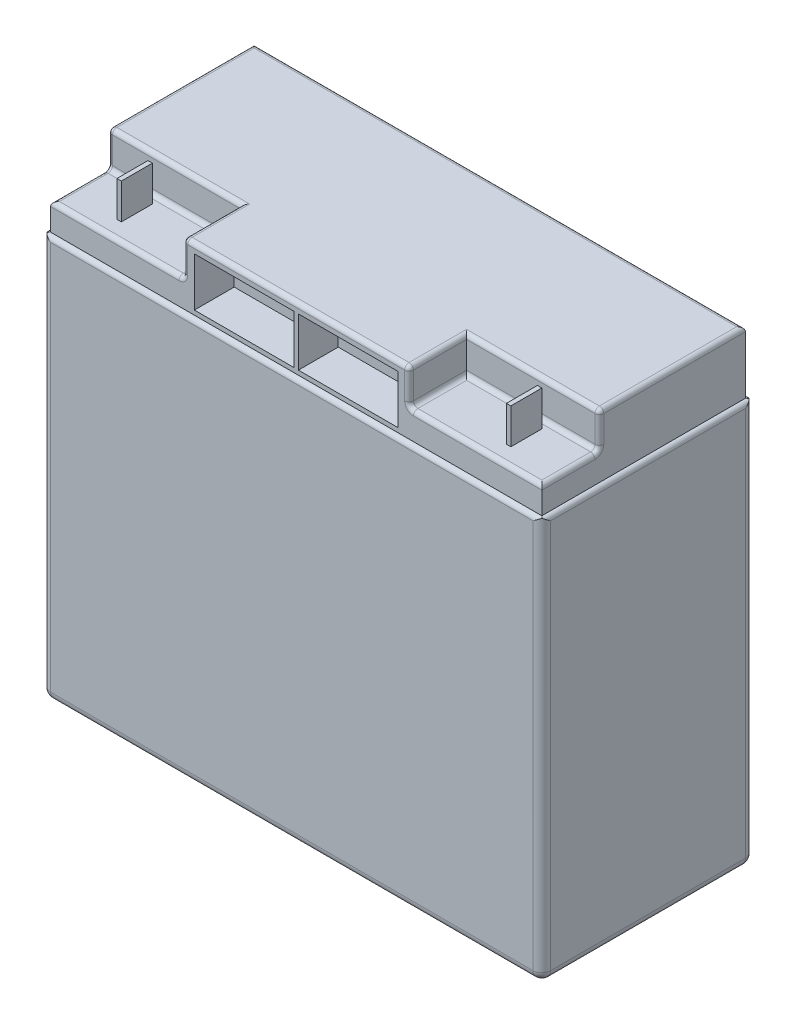
SolidWorks part; units mm, degrees
material "PE Low/Medium Density"
ref_plane "Front Plane" through (0, 0, 0) normal (0, 0, 1) x (1, 0, 0)
ref_plane "Top Plane" through (0, 0, 0) normal (0, 1, 0) x (1, 0, 0)
ref_plane "Right Plane" through (0, 0, 0) normal (1, 0, 0) x (0, 0, -1)
sketch "Sketch1" plane through (0, 0, 0) normal (0, 0, 1) x (1, 0, 0)
  line L0 (-89.6937, -83.3438) -> (89.6938, 83.3437) construction
  line L1 (-89.6938, 83.3437) -> (89.6938, 83.3437)
  line L2 (-89.6938, 83.3437) -> (-89.6937, -83.3438)
  line L3 (-89.6937, -83.3438) -> (89.6938, -83.3438)
  line L4 (89.6938, 83.3437) -> (89.6938, -83.3438)
  dimension "D1" = 166.6875
  dimension "D2" = 179.3875
extrude "Extrude1" add sketch "Sketch1" along normal mid plane 76.2
sketch "Sketch2" plane through (0, 83.3437, 0) normal (0, 1, 0) x (-1, 0, 0)
  line L10 (-89.6938, 38.1) -> (-89.6938, -38.1) construction
  line L11 (-89.6938, 38.1) -> (89.6938, 38.1) construction
  line L12 (-89.6938, -38.1) -> (89.6938, -38.1) construction
  line L13 (89.6938, 38.1) -> (89.6938, -38.1) construction
  line L14 (88.1063, -36.5125) -> (88.1063, 36.5125)
  line L15 (-88.1063, -36.5125) -> (88.1063, -36.5125)
  line L16 (-88.1063, 36.5125) -> (-88.1063, -36.5125)
  line L17 (88.1063, 36.5125) -> (-88.1063, 36.5125)
  line L18 (88.1063, -36.5125) -> (88.1063, 36.5125)
  line L19 (-88.1063, -36.5125) -> (88.1063, -36.5125)
  line L20 (-88.1063, 36.5125) -> (-88.1063, -36.5125)
  line L21 (88.1063, 36.5125) -> (-88.1063, 36.5125)
  line L22 (89.6938, 38.1) -> (89.6938, -38.1)
  line L23 (-89.6938, -38.1) -> (89.6938, -38.1)
  line L24 (-89.6938, 38.1) -> (89.6938, 38.1)
  line L25 (-89.6938, 38.1) -> (-89.6938, -38.1)
  dimension "D1" = 1.5875
extrude "Cut-Extrude1" cut sketch "Sketch2" against normal blind 22.225
sketch "Sketch3" plane through (0, 83.3437, 0) normal (0, 1, 0) x (-1, 0, 0)
  line L1 (-88.1063, 15.875) -> (-40.4812, 15.875)
  line L2 (-88.1063, 15.875) -> (-88.1063, 36.5125)
  line L3 (-88.1063, 36.5125) -> (-40.4812, 36.5125)
  line L4 (-40.4812, 15.875) -> (-40.4812, 36.5125)
  line L5 (88.1063, 15.875) -> (40.4812, 15.875)
  line L6 (88.1063, 15.875) -> (88.1063, 36.5125)
  line L7 (88.1063, 36.5125) -> (40.4812, 36.5125)
  line L8 (40.4812, 15.875) -> (40.4812, 36.5125)
  dimension "D1" = 20.6375
  dimension "D2" = 47.625
extrude "Cut-Extrude2" cut sketch "Sketch3" against normal blind 12.7
sketch "Sketch4" plane through (0, 0, 36.5125) normal (0, 0, 1) x (1, 0, 0)
  line L0 (-40.4813, 83.3437) -> (40.4812, 83.3437) construction
  line L1 (-36.5125, 80.1687) -> (-0.7938, 80.1687)
  line L2 (-36.5125, 80.1687) -> (-36.5125, 62.7062)
  line L3 (-36.5125, 62.7062) -> (-0.7938, 62.7062)
  line L4 (-0.7938, 80.1687) -> (-0.7938, 62.7062)
  line L5 (36.5125, 80.1687) -> (0.7937, 80.1687)
  line L6 (36.5125, 80.1687) -> (36.5125, 62.7062)
  line L7 (36.5125, 62.7062) -> (0.7937, 62.7062)
  line L8 (0.7937, 80.1687) -> (0.7937, 62.7062)
  dimension "D1" = 73.025
  dimension "D2" = 0.7937
  dimension "D3" = 1.5875
  dimension "D4" = 35.7188
  dimension "D5" = 3.175
  dimension "D6" = 17.4625
extrude "Cut-Extrude3" cut sketch "Sketch4" against normal blind 14.2875
mirror "Mirror1" about plane through (0, 0, 0) normal (0, 0, 1) of "Cut-Extrude3"
fillet "Fillet1" radius 1.5748 20 edges at (64.2938, 70.6437, 36.5125) (40.4812, 70.6437, 26.1938) (64.2938, 70.6437, 15.875) (88.1063, 70.6437, 26.1938) (-64.2938, 70.6437, 15.875) (-40.4812, 70.6437, 26.1937) (-64.2938, 70.6437, 36.5125) (-88.1063, 70.6437, 26.1938) (0, 83.3437, -36.5125) (88.1063, 83.3437, -10.3188) (64.2938, 83.3437, 15.875) (40.4812, 83.3437, 26.1938) (0, 83.3437, 36.5125) (-40.4813, 83.3437, 26.1937) (-64.2938, 83.3437, 15.875) (-88.1063, 83.3437, -10.3188) (89.6938, 61.1187, 0) (0, 61.1187, -38.1) (-89.6938, 61.1187, 0) (0, 61.1187, 38.1)
fillet "Fillet2" radius 3.175 8 edges at (-89.6937, -83.3438, 0) (0, -83.3438, 38.1) (89.6938, -83.3438, 0) (0, -83.3438, -38.1) (-89.6937, -11.8999, 38.1) (-89.6937, -11.8999, -38.1) (89.6938, -11.8999, 38.1) (89.6938, -11.8999, -38.1) tangent propagation no
sketch "Sketch5" plane through (0, 70.6437, 0) normal (0, 1, 0) x (-1, 0, 0)
  line L0 (-89.6938, -34.925) -> (-89.6938, 34.925) construction
  line L1 (-70.6438, 19.05) -> (-69.0563, 19.05)
  line L2 (-70.6438, 19.05) -> (-70.6438, 30.1625)
  line L3 (-70.6438, 30.1625) -> (-69.0563, 30.1625)
  line L4 (-69.0563, 19.05) -> (-69.0563, 30.1625)
  line L5 (69.0563, 19.05) -> (70.6438, 19.05)
  line L6 (69.0563, 19.05) -> (69.0563, 30.1625)
  line L7 (69.0563, 30.1625) -> (70.6438, 30.1625)
  line L8 (70.6438, 19.05) -> (70.6438, 30.1625)
  line L9 (89.6938, 34.925) -> (89.6938, -34.925) construction
  line L10 (-86.5188, 38.1) -> (86.5188, 38.1) construction
  dimension "D1" = 1.5875
  dimension "D2" = 11.1125
  dimension "D3" = 19.05
  dimension "D4" = 19.05
  dimension "D5" = 7.9375
extrude "Extrude3" add sketch "Sketch5" along normal blind 12.7
